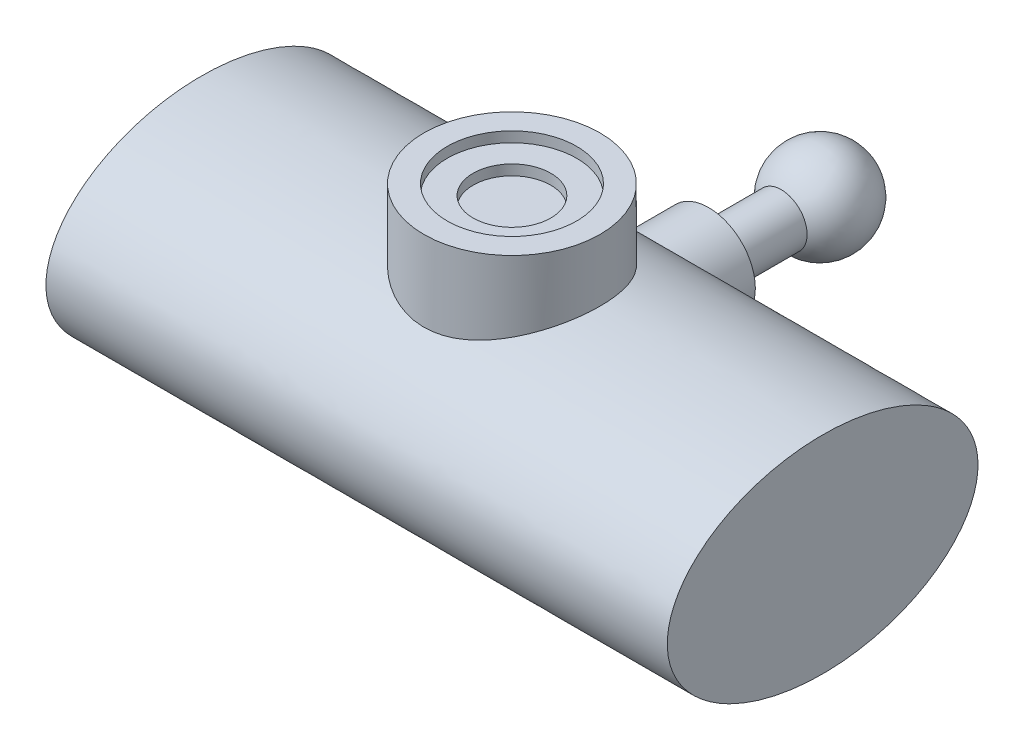
SolidWorks part; units mm, degrees
ref_plane "前视基准面" through (0, 0, 0) normal (0, 0, 1) x (1, 0, 0)
ref_plane "上视基准面" through (0, 0, 0) normal (0, 1, 0) x (1, 0, 0)
ref_plane "右视基准面" through (0, 0, 0) normal (1, 0, 0) x (0, 0, -1)
ref_axis "基准轴1" through (0, 0, -10.7037) along (0, 0, 1)
sketch "草图1" plane through (0, 0, 0) normal (0, 0, 1) x (1, 0, 0)
  circle A0 centre (0, 0) radius 2.5
  dimension "D1" = 5
extrude "凸台-拉伸1" add sketch "草图1" along normal blind 7
sketch "草图2" plane through (0, 0, 7) normal (0, 0, 1) x (1, 0, 0)
  circle A0 centre (0, 0) radius 4.5
  dimension "D1" = 9
extrude "凸台-拉伸2" add sketch "草图2" along normal blind 10
sketch "草图3" plane through (0, 0, 0) normal (1, 0, 0) x (0, 0, -1)
  ellipse E0 centre (-26, 0) end of major axis (-11, 0) minor radius 10
  dimension "D1" = 26
extrude "凸台-拉伸3" add sketch "草图3" along normal blind 30 and the other way blind 30 contours E0
sketch "草图4" plane through (0, 0, 0) normal (0, 1, 0) x (1, 0, 0)
  line L0 (2.5, 0) -> (-2.5, 0) construction
  circle A0 centre (0, -26) radius 8.5
  dimension "D1" = 26
  dimension "D2" = 17
extrude "凸台-拉伸4" add sketch "草图4" along normal blind 16
sketch "草图5" plane through (0, 16, 0) normal (0, 1, 0) x (1, 0, 0)
  circle A0 centre (0, -26) radius 6.25
  dimension "D1" = 12.5
extrude "切除-拉伸1" cut sketch "草图5" against normal blind 1
sketch "草图6" plane through (0, 15, 0) normal (0, 1, 0) x (1, 0, 0)
  circle A0 centre (0, -26) radius 3.75
  dimension "D1" = 7.5
extrude "切除-拉伸2" cut sketch "草图6" against normal blind 1
sketch "草图7" plane through (0, 0, 0) normal (0, 1, 0) x (1, 0, 0)
  line L1 (0, -0.7583) -> (0, 8.2417)
  arc A1 (0, -0.7583) -> (0, 8.2417) centre (0, 3.7417) ccw
revolve "旋转3" add sketch "草图7" angle 360 about axis through (0, 0, -10.7037) along (0, 0, 1)
